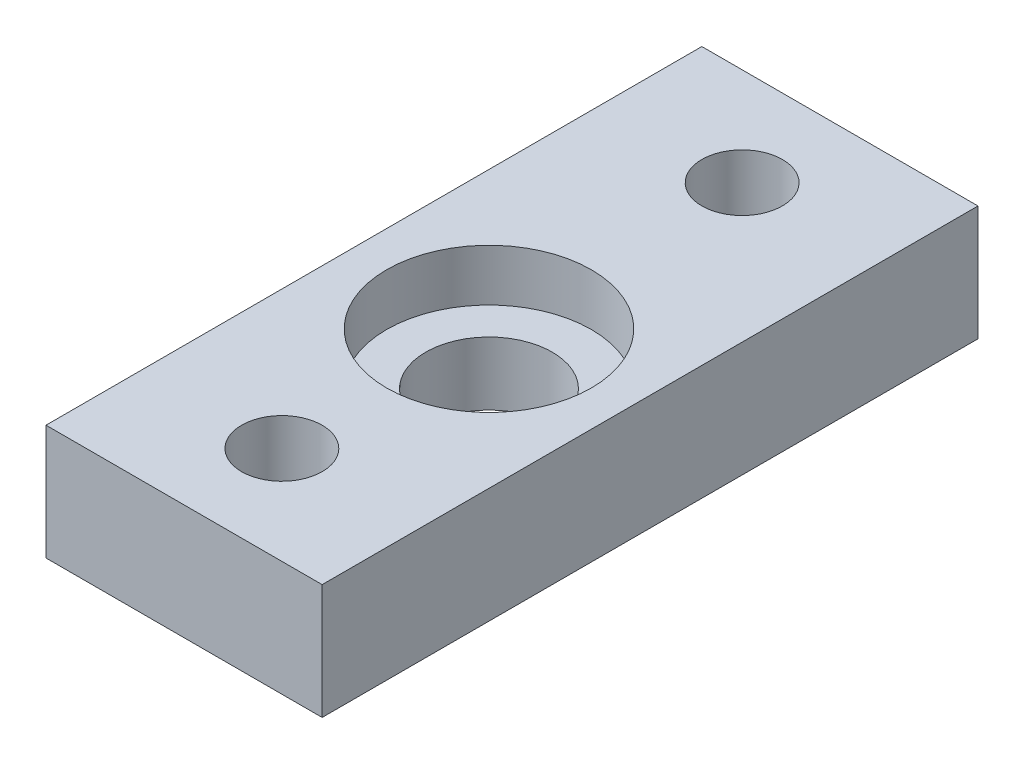
SolidWorks part; units mm, degrees
material "ABS PC"
ref_plane "Front Plane" through (0, 0, 0) normal (0, 0, 1) x (1, 0, 0)
ref_plane "Top Plane" through (0, 0, 0) normal (0, 1, 0) x (1, 0, 0)
ref_plane "Right Plane" through (0, 0, 0) normal (1, 0, 0) x (0, 0, -1)
sketch "Sketch1" plane through (0, 0, 0) normal (0, 1, 0) x (1, 0, 0)
  line L0 (0, 0) -> (0, 28.5)
  line L1 (0, 0) -> (12, 0)
  line L2 (0, 28.5) -> (12, 28.5)
  line L3 (12, 0) -> (12, 28.5)
  circle A0 centre (6, 24.25) radius 1.75
  circle A1 centre (6, 4.25) radius 1.75
  circle A2 centre (6, 13.25) radius 2.75
  dimension "D3" = 3.5
  dimension "D4" = 4.25
  dimension "D7" = 5.5
  dimension "D8" = 9
  dimension "D1" = 12
  dimension "D2" = 28.5
  dimension "D5" = 4.25
  dimension "D6" = 6
extrude "Boss-Extrude1" add sketch "Sketch1" along normal blind 5
sketch "Sketch2" plane through (0, 5, 0) normal (0, 1, 0) x (1, 0, 0)
  circle A0 centre (6, 13.25) radius 4.45
  circle A1 centre (6, 13.25) radius 2.75 construction
  dimension "D1" = 8.9
extrude "Cut-Extrude1" cut sketch "Sketch2" against normal blind 2.25
